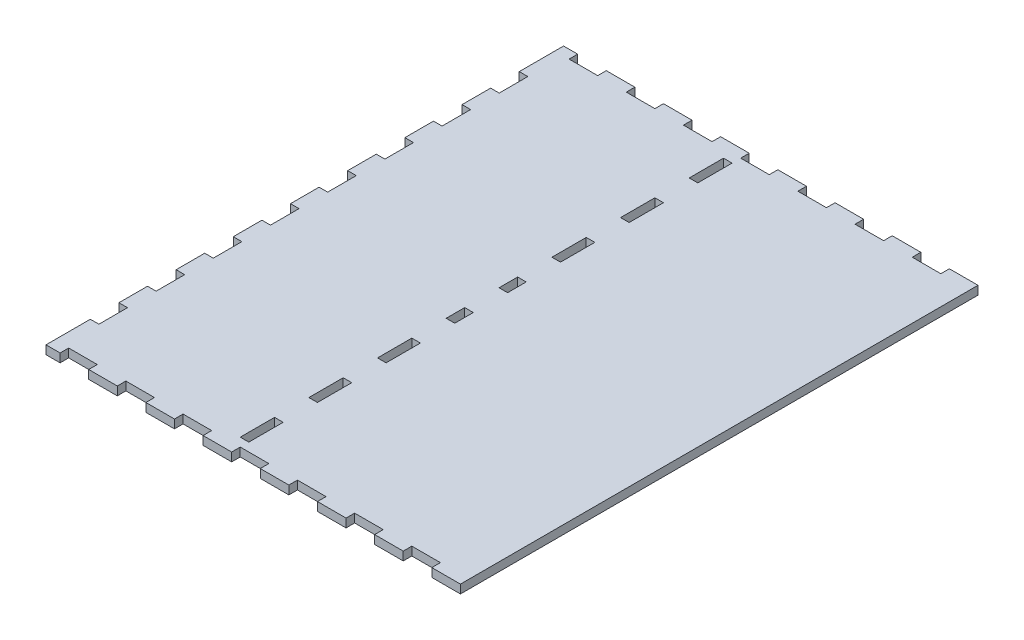
SolidWorks part; units mm, degrees
ref_plane "Front Plane" through (0, 0, 0) normal (0, 0, 1) x (1, 0, 0)
ref_plane "Top Plane" through (0, 0, 0) normal (0, 1, 0) x (1, 0, 0)
ref_plane "Right Plane" through (0, 0, 0) normal (1, 0, 0) x (0, 0, -1)
sketch "Sketch1" plane through (0, 0, 0) normal (0, 1, 0) x (1, 0, 0)
  line L0 (0, 90.5) -> (144.93, 90.5) construction
  line L2 (0, 0) -> (0, 15.5)
  line L3 (0, 181) -> (4.93, 181)
  line L4 (144.93, 0) -> (144.93, 181)
  line L5 (72.465, 181) -> (72.465, 0) construction
  line L6 (134.93, 181) -> (134.93, 178)
  line L7 (134.93, 178) -> (124.93, 178)
  line L8 (124.93, 178) -> (124.93, 181)
  line L9 (134.93, 178) -> (144.93, 178) construction
  line L10 (104.93, 178) -> (104.93, 181)
  line L11 (114.93, 178) -> (104.93, 178)
  line L12 (114.93, 181) -> (114.93, 178)
  line L13 (84.93, 178) -> (84.93, 181)
  line L14 (94.93, 178) -> (84.93, 178)
  line L15 (94.93, 181) -> (94.93, 178)
  line L16 (64.93, 178) -> (64.93, 181)
  line L17 (74.93, 178) -> (64.93, 178)
  line L18 (74.93, 181) -> (74.93, 178)
  line L19 (44.93, 178) -> (44.93, 181)
  line L20 (54.93, 178) -> (44.93, 178)
  line L21 (54.93, 181) -> (54.93, 178)
  line L22 (24.93, 178) -> (24.93, 181)
  line L23 (34.93, 178) -> (24.93, 178)
  line L24 (34.93, 181) -> (34.93, 178)
  line L25 (4.93, 178) -> (4.93, 181)
  line L26 (14.93, 178) -> (4.93, 178)
  line L27 (14.93, 181) -> (14.93, 178)
  line L28 (14.93, 181) -> (24.93, 181)
  line L29 (34.93, 181) -> (44.93, 181)
  line L30 (54.93, 181) -> (64.93, 181)
  line L31 (74.93, 181) -> (84.93, 181)
  line L32 (94.93, 181) -> (104.93, 181)
  line L33 (114.93, 181) -> (124.93, 181)
  line L34 (134.93, 181) -> (144.93, 181)
  line L35 (134.93, 3) -> (144.93, 3) construction
  line L36 (134.93, 0) -> (144.93, 0)
  line L37 (114.93, 0) -> (124.93, 0)
  line L38 (94.93, 0) -> (104.93, 0)
  line L39 (74.93, 0) -> (84.93, 0)
  line L40 (54.93, 0) -> (64.93, 0)
  line L41 (34.93, 0) -> (44.93, 0)
  line L42 (14.93, 0) -> (24.93, 0)
  line L43 (14.93, 0) -> (14.93, 3)
  line L44 (14.93, 3) -> (4.93, 3)
  line L45 (4.93, 3) -> (4.93, 0)
  line L46 (34.93, 0) -> (34.93, 3)
  line L47 (34.93, 3) -> (24.93, 3)
  line L48 (24.93, 3) -> (24.93, 0)
  line L49 (54.93, 0) -> (54.93, 3)
  line L50 (54.93, 3) -> (44.93, 3)
  line L51 (44.93, 3) -> (44.93, 0)
  line L52 (74.93, 0) -> (74.93, 3)
  line L53 (74.93, 3) -> (64.93, 3)
  line L54 (64.93, 3) -> (64.93, 0)
  line L55 (94.93, 0) -> (94.93, 3)
  line L56 (94.93, 3) -> (84.93, 3)
  line L57 (84.93, 3) -> (84.93, 0)
  line L58 (114.93, 0) -> (114.93, 3)
  line L59 (114.93, 3) -> (104.93, 3)
  line L60 (104.93, 3) -> (104.93, 0)
  line L61 (124.93, 3) -> (124.93, 0)
  line L62 (134.93, 3) -> (124.93, 3)
  line L63 (134.93, 0) -> (134.93, 3)
  line L64 (0, 0) -> (4.93, 0)
  line L65 (0, 15.5) -> (3, 15.5)
  line L66 (3, 15.5) -> (3, 25.5)
  line L67 (3, 25.5) -> (0, 25.5)
  line L68 (3, 15.5) -> (3, 0) construction
  line L69 (0, 25.5) -> (0, 35.5)
  line L70 (3, 45.5) -> (0, 45.5)
  line L71 (3, 35.5) -> (3, 45.5)
  line L72 (0, 35.5) -> (3, 35.5)
  line L73 (3, 65.5) -> (0, 65.5)
  line L74 (3, 55.5) -> (3, 65.5)
  line L75 (0, 55.5) -> (3, 55.5)
  line L76 (3, 85.5) -> (0, 85.5)
  line L77 (3, 75.5) -> (3, 85.5)
  line L78 (0, 75.5) -> (3, 75.5)
  line L79 (3, 105.5) -> (0, 105.5)
  line L80 (3, 95.5) -> (3, 105.5)
  line L81 (0, 95.5) -> (3, 95.5)
  line L82 (3, 125.5) -> (0, 125.5)
  line L83 (3, 115.5) -> (3, 125.5)
  line L84 (0, 115.5) -> (3, 115.5)
  line L85 (3, 145.5) -> (0, 145.5)
  line L86 (3, 135.5) -> (3, 145.5)
  line L87 (0, 135.5) -> (3, 135.5)
  line L88 (3, 165.5) -> (0, 165.5)
  line L89 (3, 155.5) -> (3, 165.5)
  line L90 (0, 155.5) -> (3, 155.5)
  line L91 (0, 165.5) -> (0, 181)
  line L92 (0, 145.5) -> (0, 155.5)
  line L93 (0, 125.5) -> (0, 135.5)
  line L94 (0, 105.5) -> (0, 115.5)
  line L95 (0, 45.5) -> (0, 55.5)
  line L96 (0, 65.5) -> (0, 75.5)
  line L97 (0, 85.5) -> (0, 95.5)
  dimension "D1" = 181
  dimension "D2" = 144.93
  dimension "D3" = 10
  dimension "D4" = 10
  dimension "D5" = 3
  dimension "D7" = 15.5
  dimension "D8" = 10
  dimension "D9" = 3
  dimension "D6" = 7
  dimension "D10" = 8
extrude "Boss-Extrude1" add sketch "Sketch1" along normal blind 3
sketch "Sketch2" plane through (0, 0, 0) normal (0, -1, 0) x (1, 0, 0)
  line L0 (61.93, -30) -> (61.93, -42) construction
  line L1 (61.93, -42) -> (64.93, -42) construction
  line L2 (64.93, -42) -> (64.93, -30) construction
  line L3 (64.93, -30) -> (61.93, -30) construction
  line L4 (61.93, -6) -> (61.93, -18) construction
  line L5 (61.93, -18) -> (64.93, -18) construction
  line L6 (64.93, -18) -> (64.93, -6) construction
  line L7 (64.93, -6) -> (61.93, -6) construction
  line L8 (61.93, -30) -> (61.93, -42)
  line L9 (61.93, -42) -> (64.93, -42)
  line L10 (64.93, -42) -> (64.93, -30)
  line L11 (64.93, -30) -> (61.93, -30)
  line L12 (61.93, -6) -> (61.93, -18)
  line L13 (61.93, -18) -> (64.93, -18)
  line L14 (64.93, -18) -> (64.93, -6)
  line L15 (64.93, -6) -> (61.93, -6)
  line L16 (61.93, -163) -> (61.93, -175) construction
  line L17 (61.93, -175) -> (64.93, -175) construction
  line L18 (64.93, -175) -> (64.93, -163) construction
  line L19 (64.93, -163) -> (61.93, -163) construction
  line L20 (61.93, -139) -> (61.93, -151) construction
  line L21 (61.93, -151) -> (64.93, -151) construction
  line L22 (64.93, -151) -> (64.93, -139) construction
  line L23 (64.93, -139) -> (61.93, -139) construction
  line L24 (61.93, -115) -> (61.93, -127) construction
  line L25 (61.93, -127) -> (64.93, -127) construction
  line L26 (64.93, -127) -> (64.93, -115) construction
  line L27 (64.93, -115) -> (61.93, -115) construction
  line L28 (61.93, -96.5) -> (61.93, -103) construction
  line L29 (61.93, -103) -> (64.93, -103) construction
  line L30 (64.93, -103) -> (64.93, -96.5) construction
  line L31 (64.93, -96.5) -> (61.93, -96.5) construction
  line L32 (61.93, -78) -> (61.93, -84.5) construction
  line L33 (61.93, -84.5) -> (64.93, -84.5) construction
  line L34 (64.93, -84.5) -> (64.93, -78) construction
  line L35 (64.93, -78) -> (61.93, -78) construction
  line L36 (61.93, -54) -> (61.93, -66) construction
  line L37 (61.93, -66) -> (64.93, -66) construction
  line L38 (64.93, -66) -> (64.93, -54) construction
  line L39 (64.93, -54) -> (61.93, -54) construction
  line L40 (61.93, -163) -> (61.93, -175)
  line L41 (61.93, -175) -> (64.93, -175)
  line L42 (64.93, -175) -> (64.93, -163)
  line L43 (64.93, -163) -> (61.93, -163)
  line L44 (61.93, -139) -> (61.93, -151)
  line L45 (61.93, -151) -> (64.93, -151)
  line L46 (64.93, -151) -> (64.93, -139)
  line L47 (64.93, -139) -> (61.93, -139)
  line L48 (61.93, -115) -> (61.93, -127)
  line L49 (61.93, -127) -> (64.93, -127)
  line L50 (64.93, -127) -> (64.93, -115)
  line L51 (64.93, -115) -> (61.93, -115)
  line L52 (61.93, -96.5) -> (61.93, -103)
  line L53 (61.93, -103) -> (64.93, -103)
  line L54 (64.93, -103) -> (64.93, -96.5)
  line L55 (64.93, -96.5) -> (61.93, -96.5)
  line L56 (61.93, -78) -> (61.93, -84.5)
  line L57 (61.93, -84.5) -> (64.93, -84.5)
  line L58 (64.93, -84.5) -> (64.93, -78)
  line L59 (64.93, -78) -> (61.93, -78)
  line L60 (61.93, -54) -> (61.93, -66)
  line L61 (61.93, -66) -> (64.93, -66)
  line L62 (64.93, -66) -> (64.93, -54)
  line L63 (64.93, -54) -> (61.93, -54)
extrude "Cut-Extrude1" cut sketch "Sketch2" against normal blind 10
